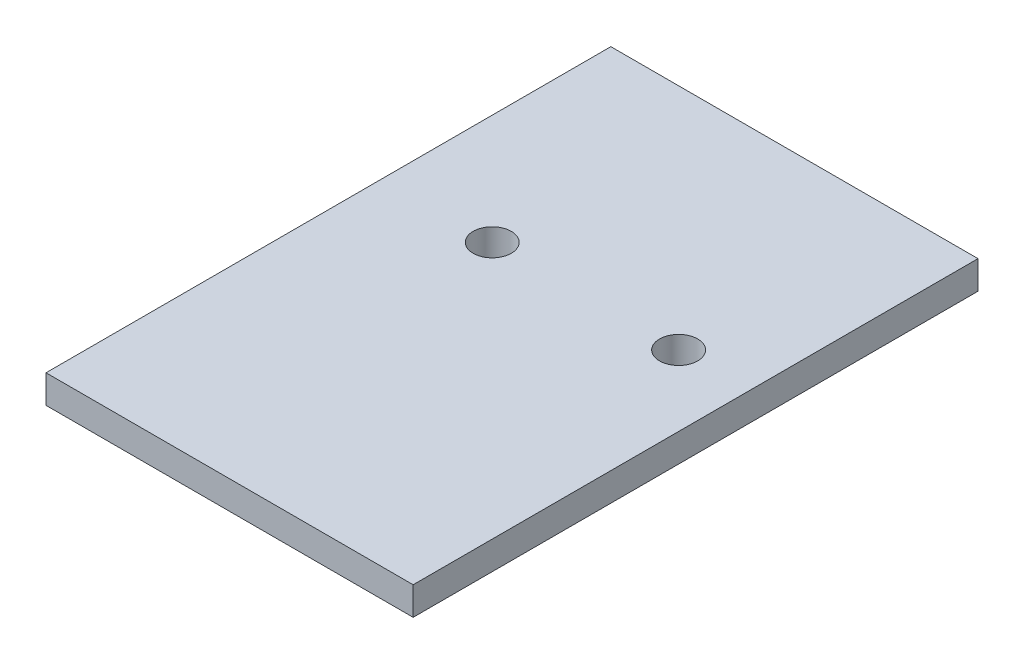
SolidWorks part; units mm, degrees
ref_plane "Front (1)" through (0, 0, 0) normal (0, 0, 1) x (1, 0, 0)
ref_plane "Top (2)" through (0, 0, 0) normal (0, 1, 0) x (1, 0, 0)
ref_plane "Right (3)" through (0, 0, 0) normal (1, 0, 0) x (0, 0, -1)
ref_axis "X-Axis" through (-80.9, 0, 0) along (1, 0, 0)
ref_axis "Y-Axis" through (0, -50, 0) along (0, 1, 0)
ref_axis "Z-Axis" through (0, 0, 50) along (0, 0, -1)
sketch "Sketch1" plane through (0, 0, 0) normal (0, 1, 0) x (1, 0, 0)
  line L0 (9.906, 30.226) -> (26.67, 30.226) construction
  line L1 (0, 0) -> (33.02, 0)
  line L2 (0, 0) -> (0, 50.8)
  line L3 (0, 50.8) -> (33.02, 50.8)
  line L4 (33.02, 0) -> (33.02, 50.8)
  circle A0 centre (9.906, 30.226) radius 1.7145
  circle A1 centre (26.67, 30.226) radius 1.7145
  dimension "D3" = 16.764
  dimension "D4" = 3.429
  dimension "D1" = 33.02
  dimension "D2" = 50.8
  dimension "D5" = 20.574
  dimension "D6" = 6.35
extrude "Boss-Extrude1" add sketch "Sketch1" along normal blind 2.54
